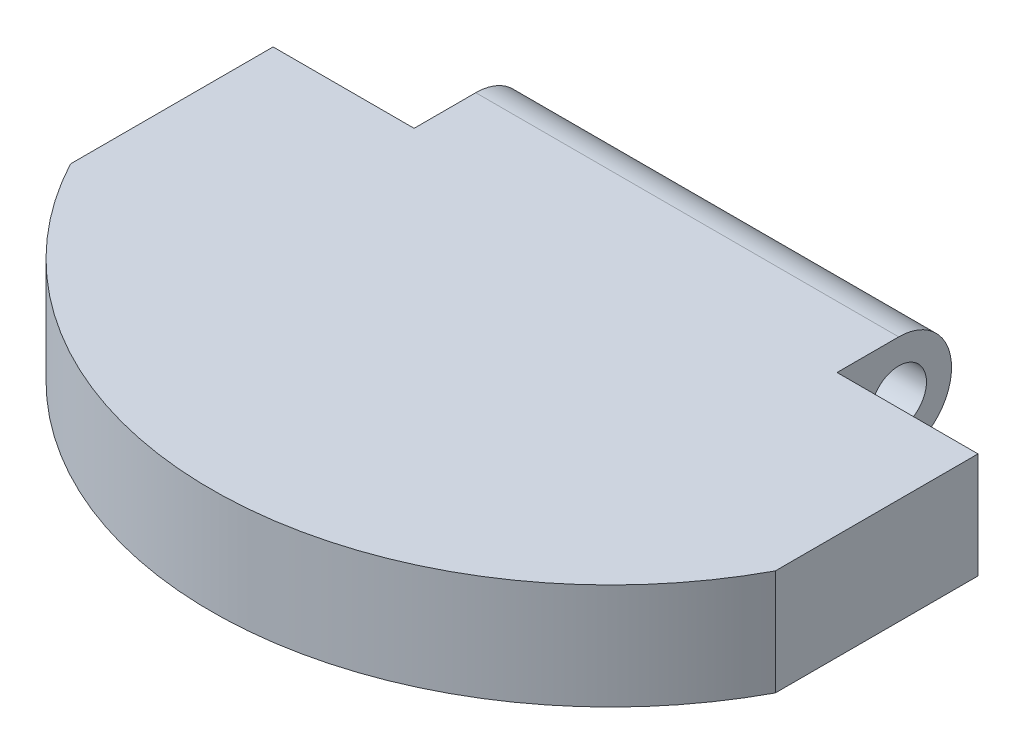
SolidWorks part; units mm, degrees
ref_plane "Front Plane" through (0, 0, 0) normal (0, 0, 1) x (1, 0, 0)
ref_plane "Top Plane" through (0, 0, 0) normal (0, 1, 0) x (1, 0, 0)
ref_plane "Right Plane" through (0, 0, 0) normal (1, 0, 0) x (0, 0, -1)
sketch "Sketch1" plane through (0, 0, 0) normal (0, 1, 0) x (1, 0, 0)
  line L1 (-40, -30) -> (40, -30)
  line L2 (-40, -30) -> (-40, 30)
  line L3 (-40, 30) -> (40, 30)
  line L4 (40, -30) -> (40, 30)
  line L5 (-40, -30) -> (40, 30) construction
  line L6 (-40, 30) -> (40, -30) construction
  line L7 (-24, 30) -> (-40, 30)
  line L8 (-24, 30) -> (-24, 17)
  line L9 (-24, 17) -> (-40, 17)
  line L10 (-40, 30) -> (-40, 17)
  line L11 (24, 30) -> (40, 30)
  line L12 (24, 30) -> (24, 17)
  line L13 (24, 17) -> (40, 17)
  line L14 (40, 30) -> (40, 17)
  arc A0 (-40, -6) -> (40, -6) centre (0, 15.3333) ccw
  point P0 (0, 0)
  point P15 (0, 0)
  dimension "D1" = 80
  dimension "D2" = 60
  dimension "D3" = 48
  dimension "D4" = 13
  dimension "D5" = 13
  dimension "D6" = 24
  dimension "D7" = 24
extrude "Boss-Extrude1" add sketch "Sketch1" along normal blind 12 contours A0 L4 L13 L12 L3 L8 L9 L2 region at (0, 0, -0.8069)
fillet "Fillet1" radius 6 2 edges at (0, 0, -30) (0, 12, -30)
sketch "Sketch2" plane through (-24, 0, 0) normal (-1, 0, 0) x (0, 0, 1)
  circle A0 centre (-24, 6) radius 3.15
  dimension "D1" = 6.3
extrude "Cut-Extrude1" cut sketch "Sketch2" against normal blind 70 contours A0
